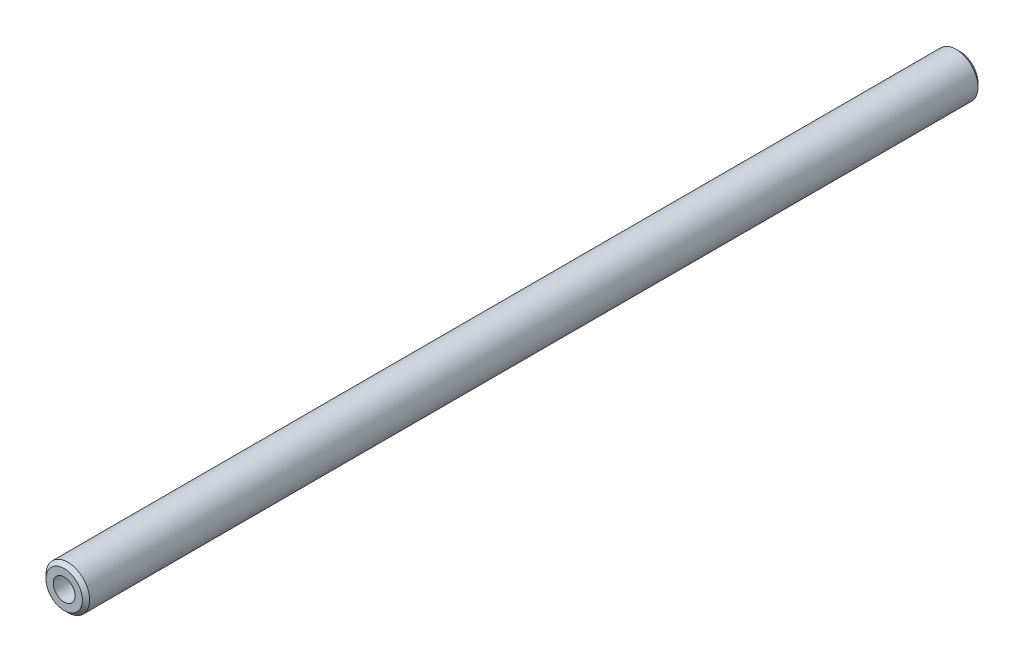
SolidWorks part; units mm, degrees
material "6061 合金"
ref_plane "前视基准面" through (0, 0, 0) normal (0, 0, 1) x (1, 0, 0)
ref_plane "上视基准面" through (0, 0, 0) normal (0, 1, 0) x (1, 0, 0)
ref_plane "右视基准面" through (0, 0, 0) normal (1, 0, 0) x (0, 0, -1)
other "Configuration Table"
sketch "草图1" plane through (0, 0, 0) normal (0, 0, 1) x (1, 0, 0)
  circle A0 centre (0, 0) radius 3
  circle A1 centre (0, 0) radius 6
  dimension "D1" = 6
  dimension "D2" = 12
extrude "凸台-拉伸1" add sketch "草图1" along normal blind 246
chamfer "倒角1" distance 1 angle 45 2 edges at (6, 0, 246) (6, 0, 0)
